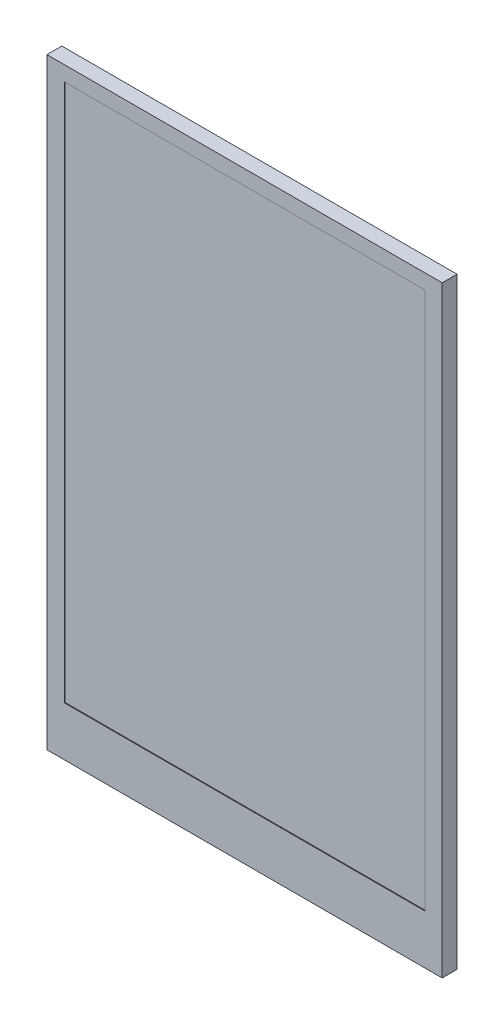
SolidWorks part; units mm, degrees
ref_plane "前视基准面" through (0, 0, 0) normal (0, 0, 1) x (1, 0, 0)
ref_plane "上视基准面" through (0, 0, 0) normal (0, 1, 0) x (1, 0, 0)
ref_plane "右视基准面" through (0, 0, 0) normal (1, 0, 0) x (0, 0, -1)
sketch "草图1" plane through (0, 0, 0) normal (0, 0, 1) x (1, 0, 0)
  line L1 (-27.23, -41.47) -> (27.23, -41.47)
  line L2 (-27.23, -41.47) -> (-27.23, 41.47)
  line L3 (-27.23, 41.47) -> (27.23, 41.47)
  line L4 (27.23, -41.47) -> (27.23, 41.47)
  line L5 (-27.23, -41.47) -> (27.23, 41.47) construction
  line L6 (-27.23, 41.47) -> (27.23, -41.47) construction
  point P0 (0, 0)
  dimension "D1" = 82.94
  dimension "D2" = 54.46
extrude "凸台-拉伸1" add sketch "草图1" along normal blind 2.05
sketch "草图2" plane through (0, 0, 2.05) normal (0, 0, 1) x (1, 0, 0)
  line L0 (27.23, -41.47) -> (27.23, 41.47) construction
  line L1 (-24.83, 39.42) -> (24.83, 39.42)
  line L2 (-24.83, 39.42) -> (-24.83, -34.67)
  line L3 (-24.83, -34.67) -> (24.83, -34.67)
  line L4 (24.83, 39.42) -> (24.83, -34.67)
  line L5 (27.23, 41.47) -> (-27.23, 41.47) construction
  point P0 (0, 0)
  dimension "D1" = 49.66
  dimension "D2" = 74.09
  dimension "D3" = 2.4
  dimension "D4" = 2.05
extrude "切除-拉伸1" cut sketch "草图2" against normal blind 0.1
ref_plane "排线起点" through (18, 0, 0) normal (1, 0, 0) x (0, 0, -1)
sketch "草图3" [suppressed] plane through (0, -41.47, 0) normal (0, -1, 0) x (1, 0, 0)
  line L1 (-14.138, 0.2) -> (17.9531, 0.2)
  line L2 (-14.138, 0.2) -> (-14.138, 0.7)
  line L3 (-14.138, 0.7) -> (17.9531, 0.7)
  line L4 (17.9531, 0.2) -> (17.9531, 0.7)
  line L5 (-27.23, 0) -> (27.23, 0) construction
  dimension "D1" = 0.2
  dimension "D2" = 0.5
extrude "排线" [suppressed] add sketch "草图3" along normal blind 44.9
sketch "草图4" [suppressed] plane through (0, 0, 0.7) normal (0, 0, 1) x (1, 0, 0)
  line L0 (1.9075, -88.9253) -> (1.9075, -26.6835) construction
  line L1 (17.9531, -86.37) -> (7.1581, -86.37)
  line L2 (17.9531, -86.37) -> (17.9531, -61.0529)
  line L3 (17.9531, -61.0529) -> (7.1581, -61.0529)
  line L4 (7.1581, -86.37) -> (7.1581, -61.0529)
  line L5 (-14.138, -86.37) -> (-6.306, -86.37)
  line L6 (-14.138, -86.37) -> (-14.138, -61.0529)
  line L7 (-14.138, -61.0529) -> (-6.306, -61.0529)
  line L8 (-6.306, -86.37) -> (-6.306, -61.0529)
  line L9 (-14.138, -41.47) -> (-7.3116, -41.47)
  line L10 (-14.138, -41.47) -> (-14.138, -45.7804)
  line L11 (-14.138, -45.7804) -> (-7.3116, -45.7804)
  line L12 (-7.3116, -41.47) -> (-7.3116, -45.7804)
  line L13 (11.1266, -41.47) -> (11.1266, -45.7804)
  line L14 (17.9531, -45.7804) -> (11.1266, -45.7804)
  line L15 (17.9531, -41.47) -> (17.9531, -45.7804)
  line L16 (17.9531, -41.47) -> (11.1266, -41.47)
extrude "切除-拉伸2" [suppressed] cut sketch "草图4" against normal blind 44.9
fillet "圆角1" [suppressed] radius 2
sketch "草图7" plane through (18, 0, 0) normal (1, 0, 0) x (0, 0, -1)
  line L0 (-2.05, -41.47) -> (0, -41.47) construction
  line L1 (2.789, -3.47) -> (3.0811, -3.4019)
  line L2 (-1.2863, -41.6174) -> (-1.025, -41.47)
  spline S0 degree 3 poles (-1.025, -41.47) (0.5863, -44.3263) (2.7242, -41.5769) (1.1674, -39.2431) (-0.4774, -35.1368) (2.4875, -28.2743) (-0.8324, -19.8778) (3.0826, -13.5873) (3.1377, -8.0992) (3.1332, -4.9465) (2.789, -3.47) knots 0 0 0 0 0.100659 0.148689 0.189271 0.409603 0.622073 0.770562 0.898771 1 1 1 1
  spline S1 degree 1 poles (-1.2863, -41.6174) (3.0811, -3.4019) knots 0 0 1 1 construction
  spline S2 degree 3 poles (-1.2863, -41.6174) (-1.2241, -41.7277) (-1.0897, -41.9519) (-0.8311, -42.3297) (-0.5035, -42.7146) (-0.1072, -43.0366) (0.4337, -43.2949) (1.1202, -43.2644) (1.7223, -42.7926) (2.1001, -42.1221) (2.2789, -41.348) (2.2096, -40.5702) (1.8491, -39.6745) (1.2647, -38.712) (0.8221, -37.5143) (0.6145, -36.2958) (0.6023, -34.6165) (0.9396, -32.4318) (1.366, -30.1677) (1.5184, -28.3197) (1.4508, -26.4654) (1.0823, -24.1981) (0.657, -21.5602) (0.6918, -19.0784) (1.5784, -16.6642) (2.7225, -14.1662) (3.348, -11.4808) (3.4239, -9.2152) (3.4329, -7.4475) (3.4269, -6.1268) (3.3427, -4.7949) (3.1871, -3.8565) (3.0811, -3.4019) knots 0 0 0 0 0.003906 0.007812 0.015625 0.023438 0.03125 0.046875 0.0625 0.078125 0.09375 0.109375 0.125 0.15625 0.1875 0.21875 0.25 0.3125 0.375 0.40625 0.4375 0.5 0.5625 0.625 0.6875 0.75 0.8125 0.875 0.90625 0.9375 0.96875 1 1 1 1
  point P2 (2.789, -3.4019)
  point P4 (0, 0)
  point P6 (3.1298, -7.7633)
  dimension "D1" = 38
  dimension "D2" = 0.3
extrude "凸台-拉伸3" add sketch "草图7" against normal blind 30 separate body
sketch "草图8" plane through (0, 0, 0) normal (0, 0, -1) x (-1, 0, 0)
  line L0 (-3, -3.4019) -> (-3, -57.7316) construction
  line L1 (12, -3.4019) -> (-18, -3.4019) construction
  line L2 (-18, 11.8658) -> (-18, -11.8658) construction
  line L3 (-18, -3.4128) -> (-11.3851, -3.4128)
  line L4 (-18, -3.4128) -> (-18, -16.1241)
  line L5 (-18, -16.1241) -> (-11.3851, -16.1241)
  line L6 (-11.3851, -3.4128) -> (-11.3851, -16.1241)
  line L7 (12, -43.2623) -> (12, -3.4019) construction
  line L8 (12, -3.4019) -> (4.3118, -3.4019)
  line L9 (12, -3.4019) -> (12, -16.1241)
  line L10 (12, -16.1241) -> (4.3118, -16.1241)
  line L11 (4.3118, -3.4019) -> (4.3118, -16.1241)
  line L12 (12, -42.8664) -> (5.0211, -42.8664)
  line L13 (12, -42.8664) -> (12, -33.9262)
  line L14 (12, -33.9262) -> (5.0211, -33.9262)
  line L15 (5.0211, -42.8664) -> (5.0211, -33.9262)
  line L17 (-18, -42.8664) -> (-10.2249, -42.8664)
  line L18 (-18, -42.8664) -> (-18, -33.9262)
  line L19 (-18, -33.9262) -> (-10.2249, -33.9262)
  line L20 (-10.2249, -42.8664) -> (-10.2249, -33.9262)
extrude "切除-拉伸4" cut sketch "草图8" along normal blind 30
sketch "草图9" [suppressed] plane through (18, 0, 0) normal (1, 0, 0) x (0, 0, -1)
  line L0 (-2.05, -41.47) -> (0, -41.47) construction
  spline S0 degree 3 poles (-1.025, -41.47) (-0.3029, -42.8154) (1.4609, -40.5258) (-1.6582, -29.2896) (3.2895, 5.2511) (5.9985, -7.8649) (6.0172, -8.5113) knots 0 0 0 0 0.054255 0.171193 0.942797 1 1 1 1
  point P2 (0.381, -40.9993)
  point P4 (-0.617, -41.9258)
  point P6 (0.064, -41.6572)
  point P8 (0.2751, -40.8419)
  point P10 (-0.522, -41.8055)
  point P12 (1.018, -30.8919)
  point P13 (1.6078, -32.3663)
  point P16 (1.7092, -33.1403)
  point P17 (0.6293, -23.4909)
  point P18 (1.1587, -24.4086)
  point P19 (1.0528, -25.9969)
  point P20 (0.8058, -21.7615)
  point P21 (1.1587, -22.6086)
  point P22 (1.0528, -21.6556)
  point P23 (1.8041, -25.9089)
  point P24 (0, 0)
  point P25 (1.5263, -26.673)
  point P26 (0, 0)
  point P27 (1.4827, -23.9144)
  point P28 (1.0377, -21.722)
  point P29 (1.6476, -26.8816)
  point P30 (0, 0)
  point P31 (1.7921, -24.3908)
  point P32 (0, 0)
  point P33 (1.5367, -22.1559)
  point P34 (1.5207, -23.0179)
  point P35 (0.9753, 0.3316)
  point P36 (1.6295, -5.6106)
  point P37 (1.7385, -6.9735)
  point P38 (1.2034, -1.7637)
  point P39 (1.2756, -2.2836)
  point P40 (1.2855, -3.6268)
  point P41 (1.3054, -4.2861)
  point P42 (1.1856, -2.7277)
  point P43 (1.5177, -5.7228)
  point P44 (1.48, -4.8184)
  point P45 (1.4046, -4.3285)
  point P46 (1.6873, -8.1156)
  point P47 (1.6873, -6.3068)
  point P48 (5.553, -8.3861)
  point P49 (4.6452, -4.6481)
  point P50 (4.05, -3.78)
  point P51 (5.1258, -4.0874)
  point P52 (4.85, -3.1796)
  point P53 (5.286, -4.4612)
  point P54 (-0.4817, -41.9994)
  point P55 (0.3937, -41.7464)
  point P56 (4.3356, -3.5664)
  point P57 (5.1878, -4.2883)
  point P58 (4.0805, -4.7995)
  point P59 (5.5345, -10.3201)
  point P60 (5.2415, -6.5551)
  point P61 (3.1247, -5.0166)
  point P62 (-1.025, -41.47)
  point P63 (-0.9315, -41.9553)
  point P64 (0.5232, -41.4851)
  point P65 (0.4204, -37.988)
  point P66 (0.1853, -41.6908)
  point P67 (0.4791, -37.7529)
  point P68 (0.969, -10.8105)
  point P69 (0, 0)
  point P70 (-0.9342, -41.9439)
  point P71 (0.3061, -41.3582)
  point P72 (0.0994, -41.7601)
  point P73 (0.2946, -36.9913)
  point P74 (2.5169, -6.6343)
  point P75 (3.9118, -8.9221)
  point P76 (3.6886, -8.9221)
  point P77 (3.6328, -13.5533)
  point P78 (3.8506, -10.232)
  point P79 (3.577, -8.9185)
  point P80 (0.639, -36.7132)
  point P81 (3.9651, -11.7944)
  point P82 (0.0589, -42.1257)
  point P83 (0.581, -41.3892)
  point P84 (3.2265, -6.6355)
  point P85 (3.503, -7.7667)
  point P86 (3.679, -8.7974)
  point P87 (6.0172, -8.5113)
  point P88 (5.7502, -6.78)
  point P89 (5.6168, -6.2611)
extrude "拉伸-薄壁2" [suppressed] add sketch "草图9" against normal blind 10 separate body thin thin type one direction wall 0.2
